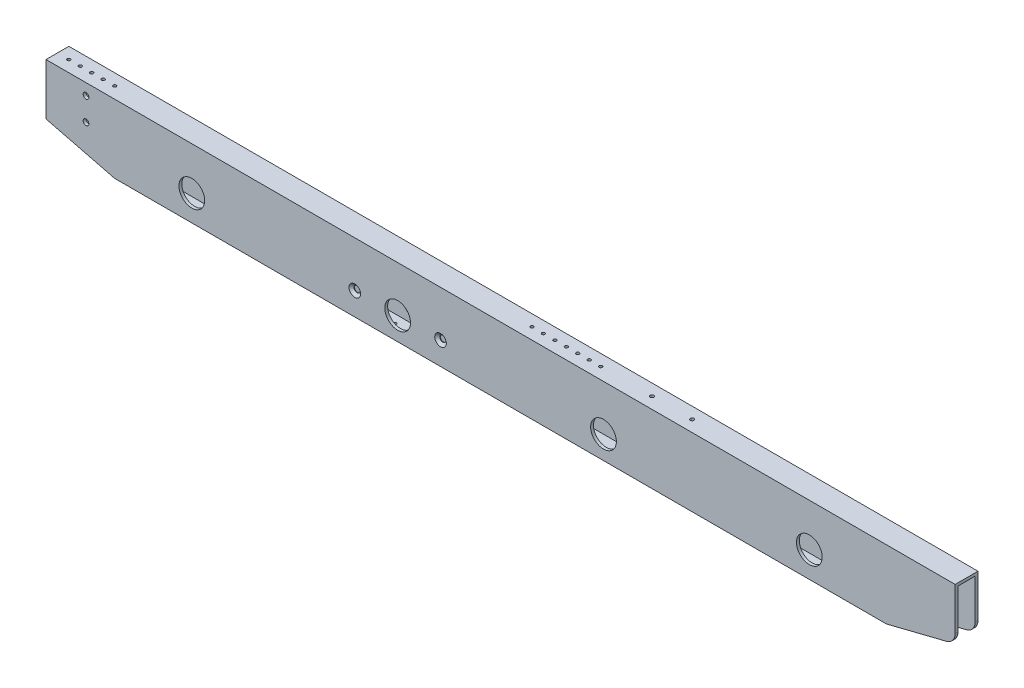
SolidWorks part; units mm, degrees
ref_plane "Front Plane" through (0, 0, 0) normal (0, 0, 1) x (1, 0, 0)
ref_plane "Top Plane" through (0, 0, 0) normal (0, 1, 0) x (1, 0, 0)
ref_plane "Right Plane" through (0, 0, 0) normal (1, 0, 0) x (0, 0, -1)
sketch "Sketch1" plane through (0, 0, 0) normal (0, 0, 1) x (1, 0, 0)
  line L0 (0, -12.7) -> (-342.9, -9.525) construction
  line L1 (-504.825, 38.1) -> (504.825, 38.1)
  line L2 (-504.825, 38.1) -> (-504.825, -38.1)
  line L3 (-504.825, -38.1) -> (504.825, -38.1)
  line L4 (504.825, 38.1) -> (504.825, -38.1)
  line L5 (-504.825, 38.1) -> (504.825, -38.1) construction
  line L6 (-504.825, -38.1) -> (504.825, 38.1) construction
  line L7 (-504.825, -38.1) -> (504.825, -38.1) construction
  line L8 (-504.825, -38.1) -> (-504.825, -12.7) construction
  line L9 (-327.025, -63.5) -> (327.025, -63.5) construction
  line L10 (-504.825, -12.7) -> (504.825, -12.7) construction
  line L11 (504.825, -38.1) -> (504.825, -12.7) construction
  line L12 (0, -12.7) -> (342.9, -9.525) construction
  line L13 (-114.3, -12.7) -> (114.3, -12.7) construction
  circle A0 centre (114.3, -12.7) radius 14.2875
  circle A1 centre (-342.9, -9.525) radius 14.2875
  circle A2 centre (342.9, -9.525) radius 14.2875
  circle A3 centre (-114.3, -12.7) radius 14.2875
  point P0 (0, 0)
  dimension "D5" = 28.575
  dimension "D4" = 28.575
  dimension "D8" = 228.6
  dimension "D6" = 228.6
  dimension "D7" = 228.6
  dimension "D1" = 76.2
  dimension "D2" = 1009.65
  dimension "D3" = 25.4
extrude "Boss-Extrude2" add sketch "Sketch1" along normal mid plane 25.4
sketch "Sketch3" plane through (504.825, 0, 0) normal (1, 0, 0) x (0, 0, -1)
  line L8 (9.525, -34.925) -> (9.525, 34.925)
  line L9 (9.525, 34.925) -> (-9.525, 34.925)
  line L10 (-9.525, 34.925) -> (-9.525, -34.925)
  line L11 (-9.525, -34.925) -> (9.525, -34.925)
  line L12 (9.525, -34.925) -> (9.525, 34.925)
  line L13 (9.525, 34.925) -> (-9.525, 34.925)
  line L14 (-9.525, 34.925) -> (-9.525, -34.925)
  line L15 (-9.525, -34.925) -> (9.525, -34.925)
  dimension "D1" = 3.175
extrude "Cut-Extrude2" cut sketch "Sketch3" against normal through all
sketch "Sketch4" plane through (0, 0, 12.7) normal (0, 0, 1) x (1, 0, 0)
  line L0 (-504.825, -38.1) -> (-504.825, -19.05)
  line L1 (-504.825, 38.1) -> (-504.825, -38.1) construction
  line L2 (-504.825, -19.05) -> (-428.625, -38.1)
  line L3 (-504.825, -38.1) -> (504.825, -38.1) construction
  line L4 (-428.625, -38.1) -> (-504.825, -38.1)
  line L5 (0, -38.1) -> (0, 38.1) construction
  line L6 (504.825, 38.1) -> (-504.825, 38.1) construction
  line L7 (428.625, -38.1) -> (504.825, -38.1)
  line L8 (504.825, -38.1) -> (504.825, -19.05)
  line L9 (504.825, -19.05) -> (428.625, -38.1)
  dimension "D1" = 19.05
  dimension "D2" = 76.2
  dimension "D3" = 57.15
extrude "Cut-Extrude3" cut sketch "Sketch4" against normal through all
fillet "Fillet1" radius 12.7 2 edges at (504.825, -19.05, -11.1125) (504.825, -19.05, 11.1125)
sketch "Sketch9" plane through (0, 38.1, 0) normal (0, 1, 0) x (1, 0, 0)
  line L0 (-504.825, -12.7) -> (-504.825, 12.7) construction
  line L1 (0, -12.7) -> (0, 12.7) construction
  line L2 (504.825, -12.7) -> (-504.825, -12.7) construction
  line L3 (504.825, 12.7) -> (-504.825, 12.7) construction
  circle A0 centre (-492.125, 0) radius 1.7272
  circle A1 centre (-441.325, 0) radius 1.7272
  circle A2 centre (-479.425, 0) radius 1.7272
  circle A3 centre (-466.725, 0) radius 1.7272
  circle A4 centre (-454.025, 0) radius 1.7272
  point P2 (-504.825, 0)
  dimension "D1" = 3.4544
  dimension "D2" = 12.7
  dimension "D3" = 4
  dimension "D4" = 2
extrude "Cut-Extrude5" cut sketch "Sketch9" against normal blind 6.35
sketch "Sketch12" plane through (0, 38.1, 0) normal (0, 1, 0) x (1, 0, 0)
  line L0 (504.825, -12.7) -> (504.825, 12.7) construction
  circle A0 centre (98.425, 0) radius 1.7272
  circle A1 centre (85.725, 0) radius 1.7272
  circle A2 centre (73.025, 0) radius 1.7272
  circle A3 centre (60.325, 0) radius 1.7272
  circle A4 centre (47.625, 0) radius 1.7272
  circle A5 centre (34.925, 0) radius 1.7272
  circle A6 centre (22.225, 0) radius 1.7272
  point P2 (504.825, 0)
  dimension "D1" = 3.4544
  dimension "D2" = 406.4
  dimension "D3" = 7
extrude "Cut-Extrude8" cut sketch "Sketch12" against normal blind 5.08
hole_wizard "CSK for 1/4 Flat Head Machine Screw (100)1" positions "Sketch14" profile "Sketch13" countersink size "1/4" standard "ANSI Inch" end condition through all
sketch "Sketch14" plane through (0, 0, 12.7) normal (0, 0, 1) x (1, 0, 0)
  circle A1 centre (-114.3, -12.7) radius 14.2875 construction
  point P0 (-66.675, -12.7)
  point P2 (-161.925, -12.7)
  dimension "D4" = 47.625
  dimension "D3" = 47.625
sketch "Sketch13" plane through (-66.675, -12.7, 12.7) normal (1, 0, 0) x (0, -1, 0)
  line L0 (0, 0) -> (0, 25.4)
  line L1 (0, 25.4) -> (3.3782, 25.4)
  line L2 (3.3782, 25.4) -> (3.3782, 2.5682)
  line L3 (3.3782, 2.5682) -> (6.4389, 0)
  line L5 (6.4389, 0) -> (0, 0)
  line L6 (-3.3782, 2.5682) -> (-6.4389, 0) construction
  line L11 (0, -6.35) -> (0, 107.95) construction
  dimension "Thru Hole Dia." = 6.7564
  dimension "Thru Hole Depth" = 25.4
  dimension "Near C'Sink Dia." = 12.8778
  dimension "Near C'Sink Angle" = 100
sketch "Sketch15" plane through (0, -38.1, 0) normal (0, -1, 0) x (-1, 0, 0)
  line L0 (428.625, 12.7) -> (428.625, -12.7) construction
  circle A0 centre (415.925, 0) radius 1.7272
  circle A1 centre (396.875, 0) radius 1.7272
  circle A2 centre (377.825, 0) radius 1.7272
  circle A3 centre (358.775, 0) radius 1.7272
  circle A4 centre (339.725, 0) radius 1.7272
  circle A5 centre (320.675, 0) radius 1.7272
  circle A6 centre (301.625, 0) radius 1.7272
  circle A7 centre (282.575, 0) radius 1.7272
  circle A8 centre (263.525, 0) radius 1.7272
  circle A9 centre (244.475, 0) radius 1.7272
  circle A10 centre (225.425, 0) radius 1.7272
  circle A11 centre (206.375, 0) radius 1.7272
  circle A12 centre (187.325, 0) radius 1.7272
  circle A13 centre (168.275, 0) radius 1.7272
  circle A14 centre (149.225, 0) radius 1.7272
  circle A15 centre (130.175, 0) radius 1.7272
  circle A16 centre (111.125, 0) radius 1.7272
  circle A17 centre (92.075, 0) radius 1.7272
  circle A18 centre (73.025, 0) radius 1.7272
  circle A19 centre (53.975, 0) radius 1.7272
  circle A20 centre (34.925, 0) radius 1.7272
  circle A21 centre (15.875, 0) radius 1.7272
  circle A22 centre (-3.175, 0) radius 1.7272
  circle A23 centre (-22.225, 0) radius 1.7272
  circle A24 centre (-41.275, 0) radius 1.7272
  circle A25 centre (-60.325, 0) radius 1.7272
  point P2 (428.625, 0)
  dimension "D1" = 3.4544
  dimension "D2" = 12.7
  dimension "D3" = 26
extrude "Cut-Extrude9" cut sketch "Sketch15" against normal blind 6.35
sketch "Sketch16" plane through (0, 0, -12.7) normal (0, 0, -1) x (-1, 0, 0)
  circle A0 centre (114.3, -12.7) radius 17.4625
  dimension "D1" = 34.925
extrude "Cut-Extrude10" cut sketch "Sketch16" against normal blind 3.81
hole_wizard "1/4 (0.25) Diameter Hole1" positions "Sketch19" profile "Sketch18" hole size "1/4" standard "ANSI Inch" end condition through all
sketch "Sketch19" plane through (0, 0, 12.7) normal (0, 0, 1) x (1, 0, 0)
  line L0 (-504.825, 38.1) -> (-504.825, -19.05) construction
  line L1 (-479.425, -25.4) -> (-479.425, 3.7361) construction
  line L2 (-428.625, -38.1) -> (-504.825, -19.05) construction
  line L5 (504.825, 38.1) -> (-504.825, 38.1) construction
  point P0 (-460.375, 25.4)
  point P2 (-460.375, 0)
  dimension "D1" = 19.05
  dimension "D2" = 25.4
  dimension "D3" = 25.4
  dimension "D4" = 12.7
sketch "Sketch18" plane through (-460.375, 25.4, 12.7) normal (1, 0, 0) x (0, -1, 0)
  line L0 (0, 0) -> (0, 25.4)
  line L1 (0, 25.4) -> (3.175, 25.4)
  line L2 (3.175, 25.4) -> (3.175, 0)
  line L5 (3.175, 0) -> (0, 0)
  line L11 (0, -6.35) -> (0, 107.95) construction
  dimension "Thru Hole Dia." = 6.35
  dimension "Thru Hole Depth" = 25.4
hole_wizard "#10-32 Tapped Hole2" positions "Sketch21" profile "Sketch20" tap size "#10-32" standard "ANSI Inch"
sketch "Sketch21" plane through (0, 38.1, 0) normal (0, 1, 0) x (1, 0, 0)
  circle A0 centre (60.325, 0) radius 1.7272 construction
  point P0 (155.575, 0)
  point P2 (200.025, 0)
  dimension "D1" = 95.25
  dimension "D2" = 44.45
cosmetic thread "Hole Thread1" parameters "D1"=3.175, "D2"=4.826
cosmetic thread "Hole Thread2" parameters "D1"=3.175, "D2"=4.826
sketch "Sketch20" plane through (155.575, 38.1, 0) normal (1, 0, 0) x (0, 0, 1)
  line L0 (0, 0) -> (0, 14.9293)
  line L1 (0, 14.9293) -> (2.0193, 13.716)
  line L2 (2.0193, 13.716) -> (2.0193, 0)
  line L5 (2.0193, 0) -> (0, 0)
  line L10 (0, 14.9293) -> (-2.0193, 13.716) construction
  line L11 (0, -6.35) -> (0, 107.95) construction
  dimension "Tap Drill Dia." = 4.0386
  dimension "Tap Drill Depth" = 13.716
  dimension "Drill Angle" = 118
